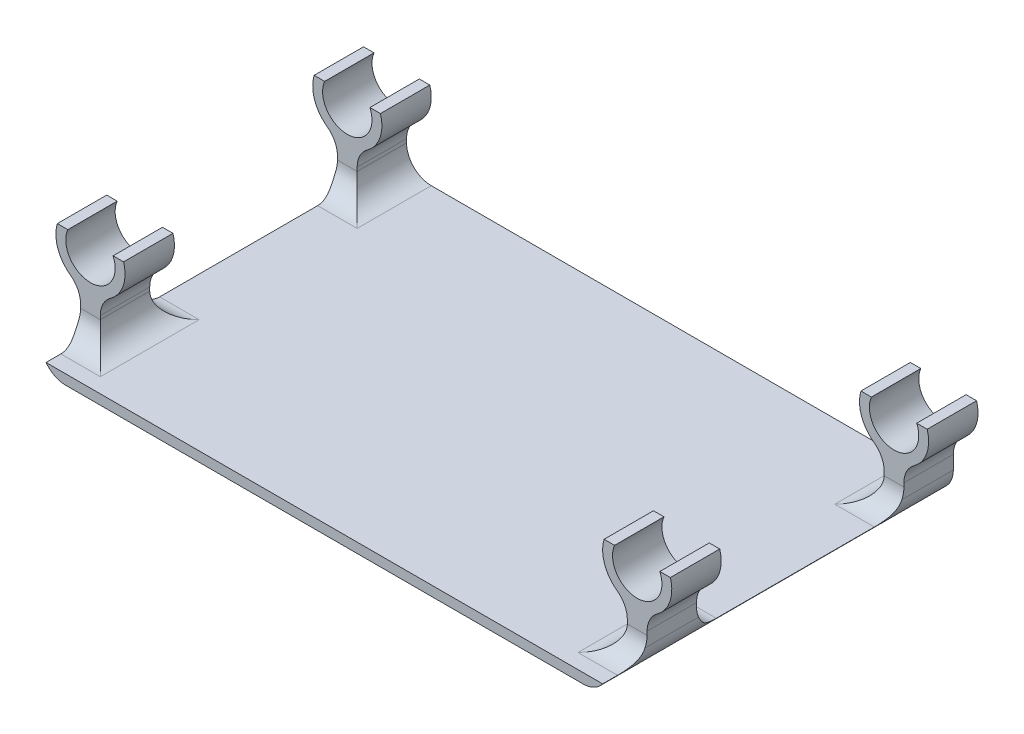
SolidWorks part; units mm, degrees
material "PLA 100% Infill"
ref_plane "Front Plane" through (0, 0, 0) normal (0, 0, 1) x (1, 0, 0)
ref_plane "Top Plane" through (0, 0, 0) normal (0, 1, 0) x (1, 0, 0)
ref_plane "Right Plane" through (0, 0, 0) normal (1, 0, 0) x (0, 0, -1)
sketch "Sketch1" plane through (0, 0, 0) normal (0, 0, 1) x (1, 0, 0)
  line L0 (-57.35, 0) -> (-57.35, 17.5) construction
  line L1 (0, 0) -> (-114.7, 0)
  line L2 (0, 0) -> (0, 2)
  line L3 (-4, 2) -> (-110.7, 2)
  line L4 (-114.7, 0) -> (-114.7, 2)
  line L5 (-53.0777, 17.5) -> (-61.6223, 17.5) construction
  line L6 (-114.7, 2) -> (-114.7, 10.7918)
  line L7 (-114.7, 10.7918) -> (-110.7, 10.7918) construction
  line L8 (-110.7, 10.7918) -> (-110.7, 2)
  line L9 (-119.4082, 19.5) -> (-117.2826, 19.5)
  line L10 (-108.1174, 19.5) -> (-105.9918, 19.5)
  line L11 (0, 2) -> (0, 10.7918)
  line L12 (-4, 10.7918) -> (-4, 2)
  line L13 (4.7082, 19.5) -> (2.5826, 19.5)
  line L14 (-6.5826, 19.5) -> (-8.7082, 19.5)
  line L15 (0, 10.7918) -> (0, 2)
  line L16 (-80.7757, 2) -> (-81.6086, 2)
  arc A0 (-117.2826, 19.5) -> (-108.1174, 19.5) centre (-112.7, 17.5) ccw
  arc A1 (-119.4082, 19.5) -> (-114.7, 10.7918) centre (-112.7, 17.5) ccw
  arc A2 (4.7082, 19.5) -> (0, 10.7918) centre (-2, 17.5) cw
  arc A3 (2.5826, 19.5) -> (-6.5826, 19.5) centre (-2, 17.5) cw
  arc A4 (-4, 10.7918) -> (-8.7082, 19.5) centre (-2, 17.5) cw
  arc A5 (-110.7, 10.7918) -> (-105.9918, 19.5) centre (-112.7, 17.5) ccw
  dimension "D2" = 10
  dimension "D1" = 17.5
  dimension "D3" = 114.7
  dimension "D4" = 2
  dimension "D5" = 4
  dimension "D7" = 2
  dimension "D8" = 2
extrude "Boss-Extrude1" add sketch "Sketch1" along normal blind 70 contours L8 A5 L10 A0 L9 A1 L6 L4 L1 L2 L11 A2 L13 A3 L14 A4 L12 L3 region at (-57.35, 1.2622, 0)
fillet "Fillet1" radius 5 8 edges at (0, 0, 35) (-114.7, 0, 35) (0, 10.7918, 35) (-4, 10.7918, 35) (-4, 2, 35) (-110.7, 2, 35) (-114.7, 10.7918, 35) (-110.7, 10.7918, 35)
sketch "Sketch2" plane through (-114.7, 0, 0) normal (-1, 0, 0) x (0, 0, 1)
  line L0 (70, 19.5) -> (0, 19.5) construction
  line L1 (10, 19.5) -> (52, 19.5)
  line L2 (10, 19.5) -> (10, 2)
  line L4 (52, 19.5) -> (52, 2)
  line L5 (52, 19.5) -> (62, 19.5)
  line L6 (0, 19.5) -> (0, 11.8144) construction
  line L8 (10, 2) -> (52, 2)
  line L9 (70, 2) -> (0, 2) construction
  line L10 (62, 19.5) -> (62, 2)
  line L11 (62, 2) -> (70, 2)
  line L12 (70, 5) -> (70, 7.7532) construction
  line L13 (62, 19.5) -> (70, 19.5)
  line L14 (70, 19.5) -> (70, 2)
  line M7 (0, 5) -> (70, 5)
  line M8 (70, 5) -> (70, 7.7532)
  line M9 (70, 7.7532) -> (0, 7.7532)
  dimension "D1" = 10
  dimension "D2" = 8
  dimension "D3" = 10
extrude "Cut-Extrude1" cut sketch "Sketch2" against normal through all and the other way through all contours L4 L1 L2 M9 | L14 L13 L10 M9 | L14 L10 L11 M7 | L10 M9 M7 M8 | L2 L8 L4 M7 | L4 L2 M9 M7 region at (-114.7, 13.6266, 31) region at (-114.7, 6.3766, 31) region at (-114.7, 13.6266, 66) region at (-114.7, 3.5, 31) region at (-114.7, 6.3766, 66) region at (-114.7, 3.5, 66)
fillet "Fillet2" radius 5 6 edges at (-5, 2, 62) (-109.7, 2, 62) (-109.7, 2, 10) (-109.7, 2, 52) (-5, 2, 52) (-5, 2, 10)
